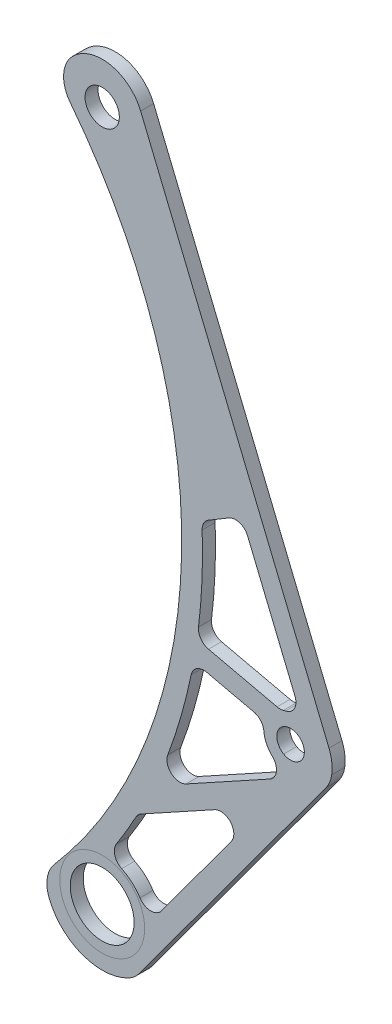
SolidWorks part; units mm, degrees
material "6061-T6 (SS)"
ref_plane "X-Y Datum" through (0, 0, 0) normal (0, 0, 1) x (1, 0, 0)
ref_plane "X-Z Datum" through (0, 0, 0) normal (0, 1, 0) x (1, 0, 0)
ref_plane "Y-Z Datum" through (0, 0, 0) normal (1, 0, 0) x (0, 0, -1)
sketch "Sketch1" plane through (0, 0, 0) normal (0, 0, 1) x (1, 0, 0)
  line L0 (0, 0) -> (0, 168.656) construction
  line L1 (0, 168.656) -> (46.0281, 56.8562) construction
  line L2 (46.0281, 56.8562) -> (0, 0) construction
  line L3 (-13.97, 0) -> (-10.16, 168.656)
  line L4 (9.3949, 172.5239) -> (55.423, 60.7241)
  line L5 (55.423, 52.9883) -> (8.1778, -11.3263)
  circle A0 centre (0, 0) radius 7.8105
  circle A1 centre (46.0281, 56.8562) radius 3.3655
  circle A2 centre (0, 168.656) radius 4.191
  arc A3 (-10.16, 168.656) -> (9.3949, 172.5239) centre (0, 168.656) cw
  arc A4 (55.423, 60.7241) -> (55.423, 52.9883) centre (46.0281, 56.8562) cw
  arc A5 (8.1778, -11.3263) -> (-13.97, 0) centre (0, 0) cw
  arc A6 (-10.16, 168.656) -> (-13.97, 0) centre (-109.3353, 86.5254) cw
  circle A7 centre (0, 0) radius 11.5718
  point P16 (56.1881, 56.8562)
  dimension "D4" = 15.621
  dimension "D5" = 6.731
  dimension "D6" = 8.382
  dimension "D7" = 13.97
  dimension "D8" = 10.16
  dimension "D9" = 10.16
  dimension "D1" = 168.656
  dimension "D2" = 120.904
  dimension "D3" = 73.152
  dimension "D11" = 125.83
extrude "Boss-Extrude1" add sketch "Sketch1" along normal blind 3.175 contours A3 A6 A5 L5 A4 L4 A2 A1 A0 | A6 A7 A0 region at (23.7229, 75.6528, 0) region at (-8.1044, 6.4136, 0)
sketch "Sketch2" plane through (0, 0, 3.175) normal (0, 0, 1) x (1, 0, 0)
  line L0 (-5.2847, 159.5355) -> (-8.7383, 6.6576)
  line L1 (8.2137, 162.0493) -> (49.1572, 62.5996)
  line L2 (10.9387, 1.0129) -> (47.2395, 50.4289)
  line L6 (-7.3221, 69.3465) -> (39.7238, 58.598)
  line L7 (43.5905, 62.9255) -> (-7.205, 74.5307)
  line L8 (-7.205, 74.5307) -> (34.1333, 99.0919)
  line L9 (-7.0697, 80.5201) -> (32.1787, 103.8395)
  line L10 (47.2395, 50.4289) -> (-8.4428, 19.7404)
  line L11 (40.0799, 40.6825) -> (-8.5754, 13.8669)
  line L12 (32.1787, 103.8395) -> (-6.2255, 117.8909)
  line L13 (29.5567, 110.2082) -> (-6.1043, 123.2559)
  line L14 (-6.1043, 123.2559) -> (13.73, 148.6504)
  line L15 (-5.9123, 131.7546) -> (11.5051, 154.0546)
  circle A1 centre (0, 168.656) radius 10.541
  circle A2 centre (0, 0) radius 10.9855
  circle A3 centre (46.0281, 56.8562) radius 6.5405
  arc A7 (3.3999, 158.6783) -> (1.1199, 10.9283) centre (-109.3353, 86.5254) cw
  arc A8 (-13.97, 0) -> (-10.16, 168.656) centre (-109.3353, 86.5254) ccw construction
  dimension "D12" = 5.08
  dimension "D7" = 5.08
  dimension "D8" = 5.08
  dimension "D9" = 5.08
  dimension "D10" = 5.08
  dimension "D11" = 5.08
extrude "Cut-Extrude1" cut sketch "Sketch2" against normal blind 6.35 contours L8 A7 L7 A3 L1 | L6 A7 L10 A3 | L11 A7 A2 L2 region at (33.8934, 78.4488, 3.175) region at (28.1628, 48.9936, 3.175) region at (17.7843, 20.3127, 3.175)
fillet "Fillet1" [suppressed] radius 2.54
sketch3d "3DSketch1" [suppressed]
  line L0 (0, 168.656, 3.175) -> (0, 168.656, 0) construction
  line L1 (46.0281, 56.8562, 3.175) -> (46.0281, 56.8562, 0) construction
  point P0 (0, 168.656, 3.175)
  point P1 (46.0281, 56.8562, 3.175)
ref_axis "Axis1" through (0, 168.656, 3.175) along (0, 0, -1)
ref_axis "Axis2" through (46.0281, 56.8562, 3.175) along (0, 0, -1)
ref_plane "Plane1" through (28.8419, 5.0856, 0) normal (0.9848, 0.1736, 0) x (0, 0, -1)
ref_plane "Plane2" through (9.9016, -5.7167, 0) normal (0.866, -0.5, 0) x (0, 0, -1)
sketch "Sketch4" [suppressed] plane through (28.8419, 5.0856, 0) normal (0.9848, 0.1736, 0) x (0, 0, -1)
  line L0 (-3.175, 166.0937) -> (-3.175, 170.2847)
sketch "Sketch5" [suppressed] plane through (9.9016, -5.7167, 0) normal (0.866, -0.5, 0) x (0, 0, -1)
  line L0 (-3.175, 72.253) -> (-3.175, 11.4039)
  line L1 (-0.3461, 48.6622) -> (-0.3461, 36.6839)
split line "Split Line1"
split line "Split Line2" [suppressed]
ref_point "Point2" [suppressed]
ref_axis "Axis3" through (0, 0, 3.175) along (0, 0, -1)
sketch "Sketch6" plane through (0, 0, 0) normal (0, 0, -1) x (-1, 0, 0)
  circle A0 centre (0, 0) radius 10.3708
split line "Split Line3"
fillet "Fillet5" radius 7.62 4 edges at (-13.97, 0, 1.5875) (-10.16, 168.656, 1.5875) (55.423, 52.9883, 1.5875) (8.1778, -11.3263, 1.5875)
fillet "Fillet6" radius 3.175 13 edges at (10.9387, 1.0129, 1.5875) (1.1199, 10.9283, 1.5875) (8.6796, 23.3767, 1.5875) (40.0799, 40.6825, 1.5875) (47.2395, 50.4289, 1.5875) (12.6076, 31.342, 1.5875) (22.351, 62.5672, 1.5875) (39.7238, 58.598, 1.5875) (49.1572, 62.5996, 1.5875) (43.5905, 62.9255, 1.5875) (23.1667, 67.5917, 1.5875) (24.3424, 93.2746, 1.5875) (34.1333, 99.0919, 1.5875)
